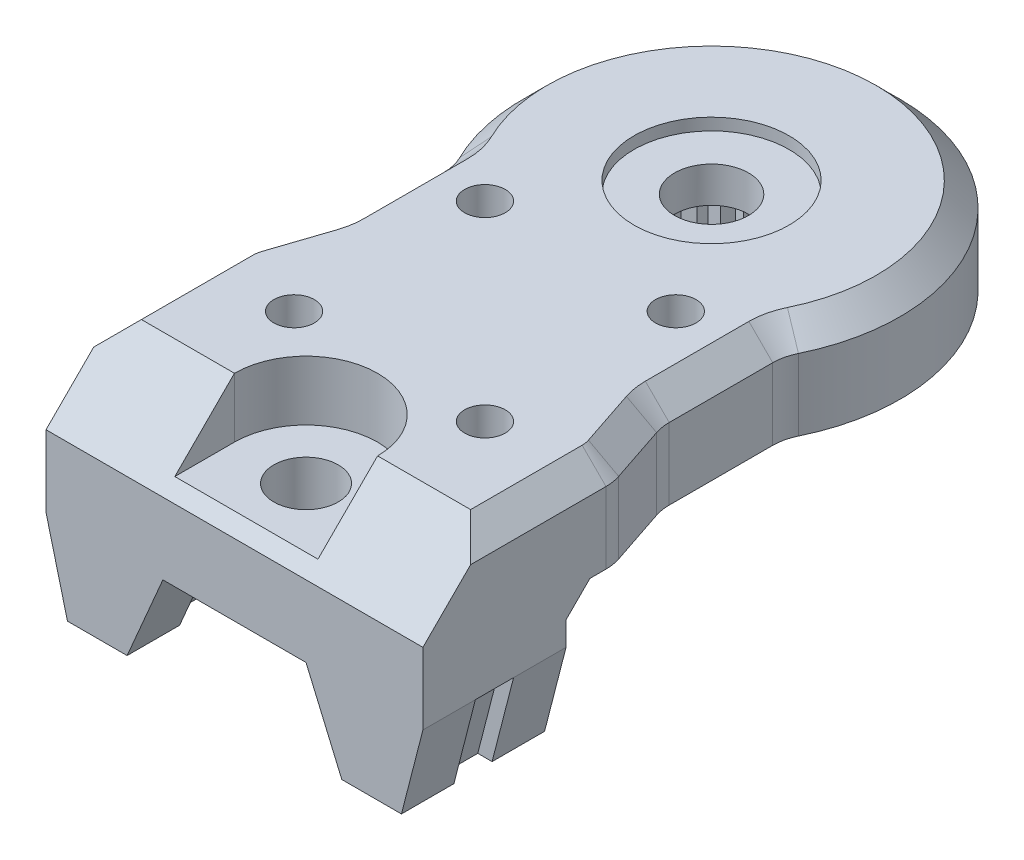
SolidWorks part; units mm, degrees
material "ABS"
ref_plane "正面" through (0, 0, 0) normal (0, 0, 1) x (1, 0, 0)
ref_plane "平面" through (0, 0, 0) normal (0, 1, 0) x (1, 0, 0)
ref_plane "右側面" through (0, 0, 0) normal (1, 0, 0) x (0, 0, -1)
sketch "ｽｹｯﾁ1" plane through (0, 0, 0) normal (0, 1, 0) x (1, 0, 0)
  line L2 (-7.9, 0) -> (-7.9, -20)
  line L3 (-7.9, -20) -> (7.9, -20)
  line L4 (7.9, 0) -> (7.9, -20)
  line L5 (-7.9, 0) -> (7.9, -20) construction
  line L6 (-7.9, -20) -> (7.9, 0) construction
  arc A0 (7.9, 0) -> (-7.9, 0) centre (0, 0) ccw
  point P7 (0, -10)
  dimension "D2" = 0
  dimension "D4" = 20
  dimension "D3" = 15.8
extrude "ﾎﾞｽ - 押し出し1" add sketch "ｽｹｯﾁ1" along normal blind 4
sketch "ｽｹｯﾁ4" plane through (0, 0, 20) normal (0, 0, 1) x (1, 0, 0)
  line L1 (-7, -5.5) -> (-4.5, -5.5)
  line L2 (-4.5, -5.5) -> (-3, -2)
  line L3 (-3, -2) -> (3, -2)
  line L4 (3, -2) -> (4.5, -5.5)
  line L5 (4.5, -5.5) -> (7, -5.5)
  line L7 (7.9, 0) -> (-7.9, 0)
  line L8 (7, -5.5) -> (7.9, -2)
  line L9 (7.9, -2) -> (7.9, 0)
  line L10 (-7, -5.5) -> (-7.9, -2)
  line L11 (-7.9, -2) -> (-7.9, 0)
  dimension "D1" = 5.5
  dimension "D2" = 3.5
  dimension "D3" = 3
  dimension "D4" = 7
  dimension "D5" = 2.5
  dimension "D9" = 2
  dimension "D10" = 2
extrude "ﾎﾞｽ - 押し出し3" add sketch "ｽｹｯﾁ4" against normal blind 6
chamfer "面取り1" distance 3 angle 45 1 edges at (0, 4, 20)
sketch "ｽｹｯﾁ5" plane through (0, 4, 0) normal (0, 1, 0) x (1, 0, 0)
  line L0 (-4, -13.5) -> (4, -13.5) construction
  line L1 (7.9, -20) -> (-7.9, -20) construction
  circle A0 centre (-4, -13.5) radius 0.85
  circle A1 centre (4, -13.5) radius 0.85
  dimension "D1" = 1.7
  dimension "D2" = 1.7
  dimension "D4" = 4
  dimension "D3" = 8
  dimension "D5" = 6.5
extrude "ｶｯﾄ - 押し出し1" cut sketch "ｽｹｯﾁ5" against normal blind 4
pattern_linear "直線ﾊﾟﾀｰﾝ1" count 2 spacing 8 along (0, 0, -1) of "ｶｯﾄ - 押し出し1"
sketch "ｽｹｯﾁ6" plane through (0, 4, 0) normal (0, 1, 0) x (1, 0, 0)
  line L0 (-3, -17) -> (-3, -21)
  line L1 (-3, -21) -> (3, -21)
  line L2 (3, -21) -> (3, -17)
  line L3 (7.9, -20) -> (-7.9, -20) construction
  arc A0 (3, -17) -> (-3, -17) centre (0, -17) ccw
  dimension "D1" = 6
  dimension "D3" = 3
  dimension "D2" = 0
  dimension "D4" = 4
extrude "ｶｯﾄ - 押し出し2" cut sketch "ｽｹｯﾁ6" against normal blind 2.5
sketch "ｽｹｯﾁ7" plane through (0, 1.5, 0) normal (0, 1, 0) x (1, 0, 0)
  circle A0 centre (0, -17) radius 1.35
  dimension "D1" = 2.7
extrude "ｶｯﾄ - 押し出し3" cut sketch "ｽｹｯﾁ7" against normal up to next
sketch "ｽｹｯﾁ8" plane through (0, 0, 0) normal (0, -1, 0) x (1, 0, 0)
  circle A0 centre (0, 0) radius 3.95
  dimension "D1" = 7.9
extrude "ﾎﾞｽ - 押し出し4" add sketch "ｽｹｯﾁ8" along normal blind 1.2
sketch "ｽｹｯﾁ9" plane through (0, 4, 0) normal (0, 1, 0) x (1, 0, 0)
  circle A0 centre (0, 0) radius 3.25
  dimension "D1" = 6.5
extrude "ｶｯﾄ - 押し出し4" cut sketch "ｽｹｯﾁ9" against normal blind 0.5
sketch "ｽｹｯﾁ10" plane through (0, 4, 0) normal (0, 1, 0) x (1, 0, 0)
  circle A0 centre (0, 0) radius 1.55
  dimension "D1" = 3.1
extrude "ｶｯﾄ - 押し出し5" cut sketch "ｽｹｯﾁ10" against normal through all
fillet "ﾌｨﾚｯﾄ1" radius 0.5 1 edges at (0, 0, 3.95)
sketch "ｽｹｯﾁ11" plane through (0, -1.2, 0) normal (0, -1, 0) x (1, 0, 0)
  circle A0 centre (0, 0) radius 3
  dimension "D1" = 6
extrude "ｶｯﾄ - 押し出し6" cut sketch "ｽｹｯﾁ11" against normal blind 3.2
sketch "ｽｹｯﾁ13" plane through (0, -1.2, 0) normal (0, -1, 0) x (1, 0, 0)
  line L0 (0, 14) -> (0, 0)
  line L1 (-3, 14) -> (3, 14) construction
sketch "ｽｹｯﾁ14" plane through (0, -1.2, 0) normal (0, -1, 0) x (1, 0, 0)
  line L0 (0, 0) -> (-0.4085, 2.9721) construction
  line L1 (-0.4085, 2.9721) -> (0, 2.5745)
  line L2 (0, 2.5745) -> (0.4085, 2.9721)
  line L3 (0.4085, 2.9721) -> (0, 0) construction
  line L4 (0, 2.5745) -> (0, 0) construction
  arc A2 (-0.4085, 2.9721) -> (0.4085, 2.9721) centre (0, 0) cw
  circle A3 centre (0, 0) radius 3 construction
  circle A4 centre (0, 0) radius 3 construction
  dimension "D1" = 0.57
  dimension "D2" = 15.652
extrude "ﾎﾞｽ - 押し出し5" add sketch "ｽｹｯﾁ14" against normal up to surface (3.2 mm away) up to face at (0, 2, -3)
pattern_circular "円形ﾊﾟﾀｰﾝ1" count 23 over 360 about axis through (0, 2, 0) along (0, -1, 0) of "ﾎﾞｽ - 押し出し5"
ref_plane "平面1" through (0, 0, 17) normal (0, 0, 1) x (1, 0, 0)
sketch "ｽｹｯﾁ15" plane through (0, 0, 17) normal (0, 0, 1) x (1, 0, 0)
  line L0 (3, -2) -> (4.5, -5.5)
  line L1 (4.5, -5.5) -> (5.1, -5.5)
  line L2 (4.5, -5.5) -> (7, -5.5) construction
  line L3 (5.1, -5.5) -> (3.6, -2)
  line L4 (3.6, -2) -> (3, -2)
  line L5 (7.9, -2) -> (7.3, -2)
  line L6 (7.3, -2) -> (6.4, -5.5)
  line L7 (6.4, -5.5) -> (7, -5.5)
  line L8 (7, -5.5) -> (7.9, -2) construction
  line L9 (7.9, -2) -> (7, -5.5)
  dimension "D1" = 0.6
  dimension "D2" = 0.6
extrude "ｶｯﾄ - 押し出し7" cut sketch "ｽｹｯﾁ15" against normal mid plane 1.6
mirror "ﾐﾗｰ1" about plane through (0, 0, 0) normal (1, 0, 0) of "ｶｯﾄ - 押し出し7"
sketch "ｽｹｯﾁ16" plane through (0, 4, 0) normal (0, 1, 0) x (1, 0, 0)
  line L0 (-7.9, 0) -> (-7.9, -12)
  line L1 (-7.9, 0) -> (-7.9, -17) construction
  line L2 (-7.9, -12) -> (-6.9, -9)
  line L3 (-6.9, -9) -> (-6.9, -3.8471)
  line L4 (7.9, -20) -> (-7.9, -20) construction
  arc A0 (-7.9, 0) -> (-6.9, -3.8471) centre (0, 0) ccw
  arc A1 (7.9, 0) -> (-7.9, 0) centre (0, 0) ccw construction
  dimension "D1" = 6.9
  dimension "D2" = 3
  dimension "D3" = 11
extrude "ｶｯﾄ - 押し出し8" cut sketch "ｽｹｯﾁ16" against normal through all
mirror "ﾐﾗｰ4" about plane through (0, 0, 0) normal (1, 0, 0) of "ｶｯﾄ - 押し出し8"
fillet "ﾌｨﾚｯﾄ2" radius 2 6 edges at (6.9, 2, 3.8471) (6.9, 2, 9) (7.9, 2, 12) (-6.9, 2, 9) (-7.9, 2, 12) (-6.9, 2, 3.8471)
chamfer "面取り2" distance 1 angle 45 16 edges at (-7.9, 4, 14.6623) (0, 4, -7.9) (7.9, 4, 14.6623) (6.2937, 0, 14) (-6.2937, 0, 14) (-7.8742, 4, 12.0042) (-7.4, 4, 10.5) (-6.9258, 4, 8.9958) (-6.9, 4, 6.5057) (-6.9512, 4, 3.8864) (6.9512, 4, 3.8864) (6.9, 4, 6.5057) (6.9258, 4, 8.9958) (7.4, 4, 10.5) (7.8742, 4, 12.0042) (0, 0, 14)
